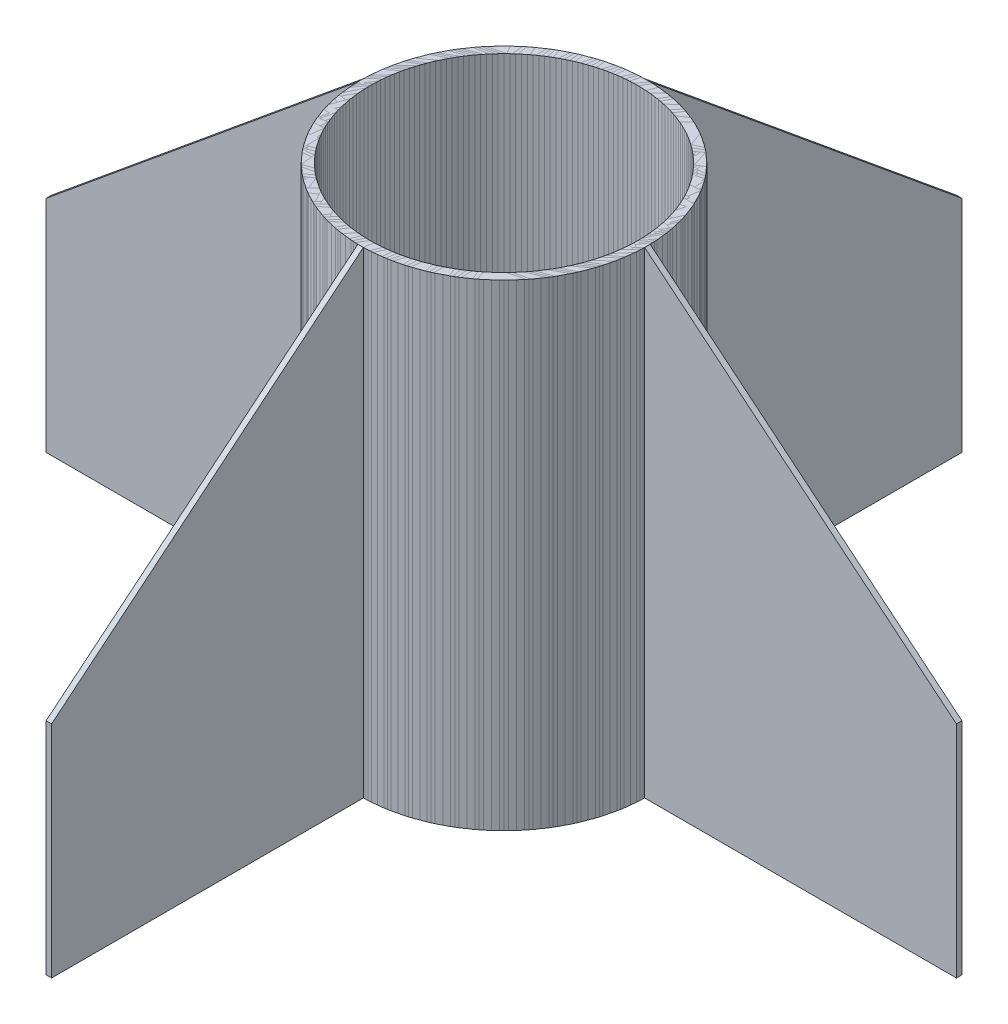
SolidWorks part; units mm, degrees
material "Commercially Pure grade 2 longitudinal (SS)"
ref_plane "Front Plane" through (0, 0, 0) normal (0, 0, 1) x (1, 0, 0)
ref_plane "Top Plane" through (0, 0, 0) normal (0, 1, 0) x (1, 0, 0)
ref_plane "Right Plane" through (0, 0, 0) normal (1, 0, 0) x (0, 0, -1)
sketch "Sketch1" plane through (0, 0, 0) normal (0, 1, 0) x (1, 0, 0)
  circle A0 centre (0, 0) radius 78.2
  circle A1 centre (0, 0) radius 73.2
  dimension "D1" = 156.4
  dimension "D2" = 146.4
extrude "Boss-Extrude1" add sketch "Sketch1" along normal blind 260
sketch "Sketch2" plane through (0, 0, 0) normal (0, 0, 1) x (1, 0, 0)
  line L0 (78.2, 0) -> (78.2, 260) construction
  line L1 (78.2, 0) -> (78.2, 260)
  line L2 (78.2, 0) -> (248.2, 0)
  line L3 (248.2, 0) -> (248.2, 120)
  line L4 (248.2, 120) -> (78.2, 260)
  dimension "D1" = 170
  dimension "D2" = 120
extrude "Boss-Extrude2" add sketch "Sketch2" along normal blind 1.5 and the other way blind 1.5 separate body
sketch "Sketch4" plane through (0, 0, 0) normal (0, 0, 1) x (1, 0, 0)
  line L0 (78.2, 260) -> (78.2, 0) construction
  line L1 (78.2, 260) -> (78.2, 0)
  line L2 (78.2, 260) -> (76.2, 260)
  line L3 (78.2, 260) -> (-78.2, 260) construction
  line L4 (76.2, 260) -> (76.2, 0)
  line L5 (-78.2, 0) -> (78.2, 0) construction
  line L6 (76.2, 0) -> (78.2, 0)
  point P2 (78.2, 130)
  dimension "D1" = 2
extrude "Boss-Extrude3" add sketch "Sketch4" along normal blind 1.5 and the other way blind 1.5
pattern_circular "CirPattern1" count 4 over 360 about axis through (0, 260, 0) along (0, -1, 0) of bodies 103
